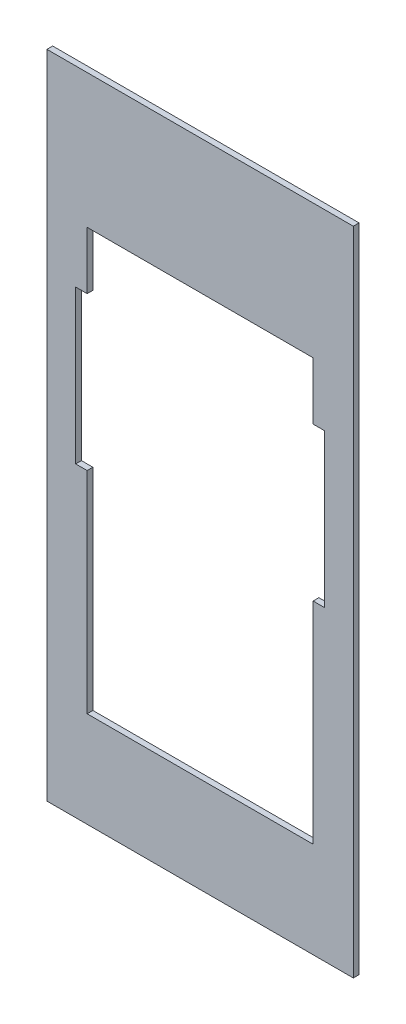
SolidWorks part; units mm, degrees
ref_plane "Front Plane" through (0, 0, 0) normal (0, 0, 1) x (1, 0, 0)
ref_plane "Top Plane" through (0, 0, 0) normal (0, 1, 0) x (1, 0, 0)
ref_plane "Right Plane" through (0, 0, 0) normal (1, 0, 0) x (0, 0, -1)
sketch "Sketch1" plane through (0, 0, 0) normal (0, 0, 1) x (1, 0, 0)
  line L1 (-40, 85) -> (40, 85)
  line L2 (-40, 85) -> (-40, -85)
  line L3 (-40, -85) -> (40, -85)
  line L4 (40, 85) -> (40, -85)
  line L5 (-40, 85) -> (40, -85) construction
  line L6 (-40, -85) -> (40, 85) construction
  line L20 (0, 0) -> (0, 97.4562) construction
  line L21 (0, 0) -> (0, -80.4119) construction
  line L22 (-29.5, -5) -> (-29.5, -60)
  line L23 (-29.5, 50) -> (29.5, 50)
  line L24 (-29.5, 50) -> (-29.5, 35)
  line L25 (-29.5, -60) -> (29.5, -60)
  line L26 (29.5, 50) -> (29.5, 35)
  line L27 (-29.5, 50) -> (29.5, -60) construction
  line L28 (-29.5, -60) -> (29.5, 50) construction
  line L29 (-29.5, 35) -> (-32.5, 35)
  line L31 (-29.5, -5) -> (-32.5, -5)
  line L32 (-32.5, 35) -> (-32.5, -5)
  line L33 (29.5, 35) -> (32.5, 35)
  line L35 (29.5, -5) -> (32.5, -5)
  line L36 (32.5, 35) -> (32.5, -5)
  line L37 (29.5, -5) -> (29.5, -60)
  point P0 (0, 0)
  point P6 (0, -5)
  dimension "D2" = 80
  dimension "D3" = 3
  dimension "D4" = 3
  dimension "D5" = 170
  dimension "D6" = 35
  dimension "D7" = 40
  dimension "D8" = 40
  dimension "D9" = 25
  dimension "D10" = 15
  dimension "D11" = 15
  dimension "D12" = 59
extrude "Boss-Extrude1" add sketch "Sketch1" along normal blind 1.5
